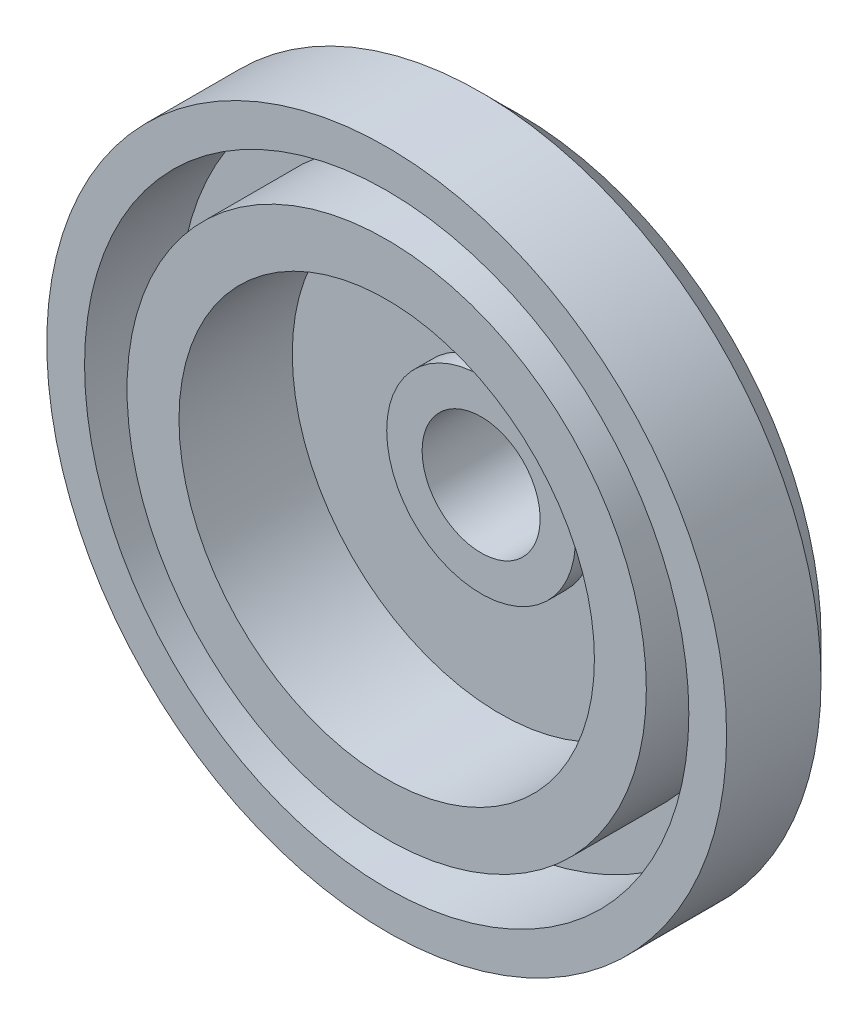
SolidWorks part; units mm, degrees
ref_plane "Plan de face" through (0, 0, 0) normal (0, 0, 1) x (1, 0, 0)
ref_plane "Plan de dessus" through (0, 0, 0) normal (0, 1, 0) x (1, 0, 0)
ref_plane "Plan de droite" through (0, 0, 0) normal (1, 0, 0) x (0, 0, -1)
sketch "Esquisse1" plane through (0, 0, 0) normal (0, 0, 1) x (1, 0, 0)
  circle A0 centre (0, 0) radius 13.75
  circle A1 centre (0, 0) radius 16
  circle A2 centre (0, 0) radius 18
  circle A3 centre (0, 0) radius 11
  dimension "D1" = 27.5
  dimension "D2" = 32
  dimension "D3" = 36
  dimension "D4" = 22
extrude "Boss.-Extru.1" add sketch "Esquisse1" along normal blind 7 contours A2 A1 | A0 A3 region at (-13.3611, 0, 0) region at (-17.4909, 0, 0)
extrude "Boss.-Extru.2" add sketch "Esquisse1<3>" along normal blind 2 contours A1 A0 region at (-15.5475, 0, 0)
sketch "Esquisse1<3>" plane through (0, 0, 0) normal (0, 0, 1) x (1, 0, 0) same geometry as "Esquisse1"
chamfer "Chanfrein1" distance 2 angle 45 1 edges at (18, 0, 0)
sketch "Esquisse3" plane through (0, 0, 0) normal (0, 0, -1) x (-1, 0, 0)
  circle A0 centre (0, 0) radius 3.125
  circle A1 centre (0, 0) radius 5
  dimension "D1" = 6.25
  dimension "D2" = 10
extrude "Boss.-Extru.3" add sketch "Esquisse3" against normal blind 2 and the other way blind 4 separate body
sketch "Esquisse4" plane through (0, 0, 0) normal (0, 0, -1) x (-1, 0, 0)
  circle A0 centre (0, 0) radius 11
  circle A1 centre (0, 0) radius 3.8345
extrude "Boss.-Extru.4" add sketch "Esquisse4" against normal blind 1
